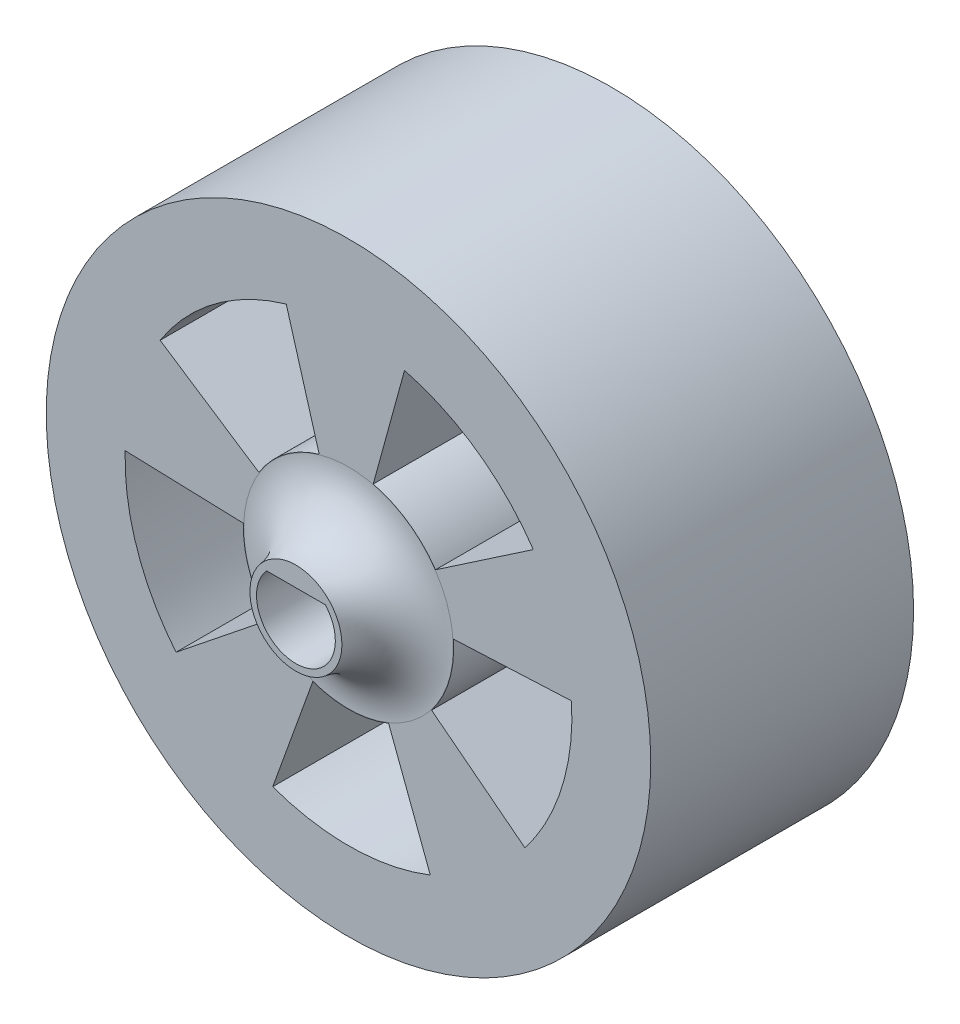
SolidWorks part; units mm, degrees
ref_plane "Front Plane" through (0, 0, 0) normal (0, 0, 1) x (1, 0, 0)
ref_plane "Top Plane" through (0, 0, 0) normal (0, 1, 0) x (1, 0, 0)
ref_plane "Right Plane" through (0, 0, 0) normal (1, 0, 0) x (0, 0, -1)
sketch "Sketch1" plane through (0, 0, 0) normal (0, 0, 1) x (1, 0, 0)
  circle A0 centre (0, 0) radius 11.5
  dimension "D1" = 23
extrude "Boss-Extrude1" add sketch "Sketch1" along normal blind 10
sketch "Sketch2" plane through (0, 0, 10) normal (0, 0, 1) x (1, 0, 0)
  circle A0 centre (0, 0) radius 8.5
  dimension "D1" = 17
extrude "Cut-Extrude2" cut sketch "Sketch2" against normal blind 10
sketch "Sketch4" plane through (0, 0, 0) normal (0, 0, 1) x (1, 0, 0)
  circle A0 centre (0, 0) radius 4
  dimension "D1" = 8
extrude "Boss-Extrude2" add sketch "Sketch4" along normal blind 10 separate body
sketch "Sketch6" plane through (0, 0, 0) normal (0, 0, 1) x (1, 0, 0)
  line L0 (-1.1144, 3.8416) -> (-2.3682, 8.1634)
  line L1 (0.9403, 3.8879) -> (2.1318, 8.2283)
  circle A0 centre (0, 0) radius 4 construction
  circle A1 centre (0, 0) radius 8.5 construction
  arc A2 (-2.3682, 8.1634) -> (2.1318, 8.2283) centre (0, 0) cw
  arc A3 (0.9403, 3.8879) -> (-1.1144, 3.8416) centre (0, 0) ccw
  dimension "D1" = 4.5
  dimension "D2" = 2.0553
extrude "Boss-Extrude3" add sketch "Sketch6" along normal blind 10
pattern_circular "CirPattern1" count 5 every 72 about axis through (0, 0, 10) along (0, 0, 1) of "Boss-Extrude3"
sketch "Sketch7" plane through (0, 0, 10) normal (0, 0, 1) x (1, 0, 0)
  line L0 (-1.118, 1) -> (1.118, 1)
  arc A0 (-1.118, 1) -> (1.118, 1) centre (0, 0) ccw
  dimension "D1" = 3
  dimension "D2" = 1
extrude "Cut-Extrude4" cut sketch "Sketch7" against normal blind 10
sketch "Sketch8" plane through (0, 0, 10) normal (0, 0, 1) x (1, 0, 0)
  circle A0 centre (0, 0) radius 1.75
  dimension "D1" = 3.5
extrude "Boss-Extrude4" add sketch "Sketch8" along normal blind 2
sketch "Sketch9" plane through (0, 0, 12) normal (0, 0, 1) x (1, 0, 0)
  line L0 (-1.118, 1) -> (1.118, 1)
  arc A0 (-1.118, 1) -> (1.118, 1) centre (0, 0) ccw
  dimension "D1" = 3
  dimension "D2" = 1
extrude "Cut-Extrude5" cut sketch "Sketch9" against normal blind 2
fillet "Fillet1" radius 2.25 1 edges at (1.75, 0, 10)
